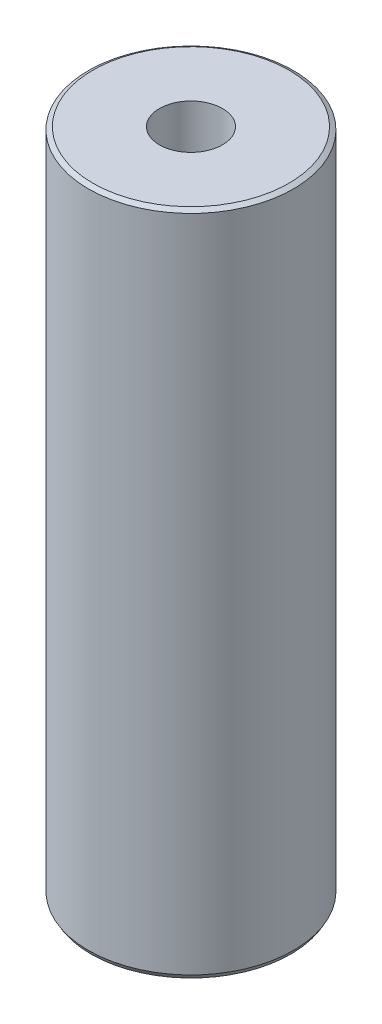
SolidWorks part; units mm, degrees
ref_plane "Front Plane" through (0, 0, 0) normal (0, 0, 1) x (1, 0, 0)
ref_plane "Top Plane" through (0, 0, 0) normal (0, 1, 0) x (1, 0, 0)
ref_plane "Right Plane" through (0, 0, 0) normal (1, 0, 0) x (0, 0, -1)
sketch "Sketch1" plane through (0, 0, 0) normal (0, 1, 0) x (1, 0, 0)
  circle A0 centre (0, 0) radius 57.5
  dimension "SHAFT_OD" = 115
extrude "Boss-Extrude1" add sketch "Sketch1" along normal blind 373.8176
sketch "Sketch2" plane through (0, 0, 0) normal (0, 1, 0) x (1, 0, 0)
  circle A0 centre (0, 0) radius 17.6763
  dimension "BORE_D" = 35.3526
extrude "Cut-Extrude1" cut sketch "Sketch2" along normal through all
chamfer "Chamfer1" distance 1.4752 angle 59.839 2 edges at (0, 373.8176, 57.5) (0, 0, 57.5) first distance on face at (0, 373.8176, 57.5) first distance on face at (0, 0, 17.6763)
